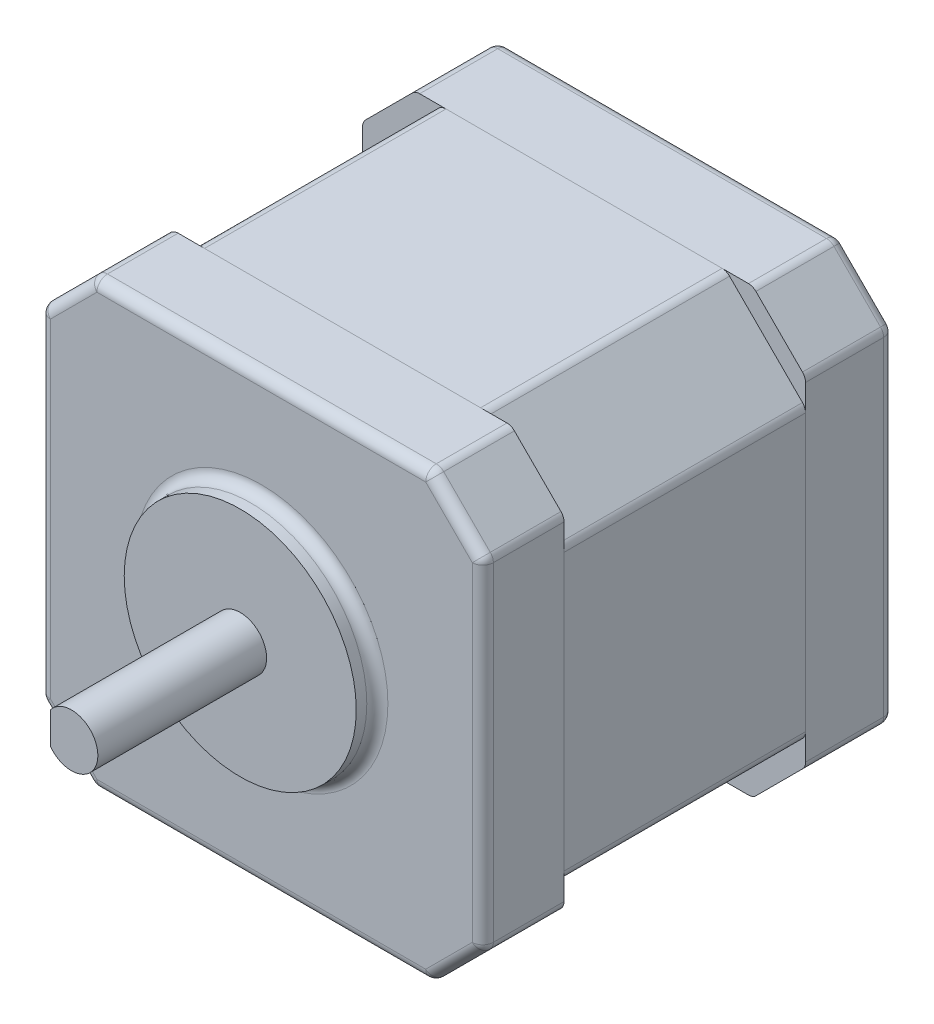
SolidWorks part; units mm, degrees
material "AISI 1020"
ref_plane "Front Plane" through (0, 0, 0) normal (0, 0, 1) x (1, 0, 0)
ref_plane "Top Plane" through (0, 0, 0) normal (0, 1, 0) x (1, 0, 0)
ref_plane "Right Plane" through (0, 0, 0) normal (1, 0, 0) x (0, 0, -1)
sketch "Sketch1" plane through (0, 0, 0) normal (0, 0, 1) x (1, 0, 0)
  line L1 (-21, -21) -> (21, -21)
  line L2 (-21, -21) -> (-21, 21)
  line L3 (-21, 21) -> (21, 21)
  line L4 (21, -21) -> (21, 21)
  line L5 (-21, -21) -> (21, 21) construction
  line L6 (-21, 21) -> (21, -21) construction
  point P0 (0, 0)
  dimension "D1" = 42
extrude "Boss-Extrude1" add sketch "Sketch1" along normal mid plane 39
sketch "Sketch2" plane through (0, 0, 19.5) normal (0, 0, 1) x (1, 0, 0)
  line L0 (-21, 21) -> (-13.5, 21)
  line L1 (21, 21) -> (-21, 21) construction
  line L2 (-13.5, 21) -> (-21, 13.5)
  line L3 (-21, 21) -> (-21, -21) construction
  line L4 (-21, 13.5) -> (-21, 21)
  line L5 (13.5, 21) -> (21, 21)
  line L6 (21, 13.5) -> (13.5, 21)
  line L7 (21, 21) -> (21, 13.5)
  line L8 (21, -13.5) -> (21, -21)
  line L9 (13.5, -21) -> (21, -13.5)
  line L10 (21, -21) -> (13.5, -21)
  line L11 (-13.5, -21) -> (-21, -21)
  line L12 (-21, -13.5) -> (-13.5, -21)
  line L13 (-21, -21) -> (-21, -13.5)
  line L14 (0, 0) -> (-13.5, 21) construction
  line L15 (-21, -21) -> (21, -21) construction
  dimension "D1" = 7.5
  dimension "D3" = 24.965
  dimension "D2" = 4
extrude "Cut-Extrude1" cut sketch "Sketch2" against normal blind 22.9 from offset 7.7 offset against normal yes
sketch "Sketch3" plane through (0, 0, 19.5) normal (0, 0, 1) x (1, 0, 0)
  circle A0 centre (0, 0) radius 11
  dimension "D1" = 22
extrude "Boss-Extrude2" add sketch "Sketch3" along normal blind 2
chamfer "Chamfer1" distance 5 angle 45 8 edges at (21, 21, -15.3) (21, 21, 15.65) (21, -21, 15.65) (21, -21, -15.3) (-21, 21, -15.3) (-21, -21, -15.3) (-21, -21, 15.65) (-21, 21, 15.65)
fillet "Fillet1" radius 1 41 edges at (-18.5, 18.5, -19.5) (-21, 0, -19.5) (-18.5, -18.5, -19.5) (0, -21, -19.5) (18.5, -18.5, -19.5) (21, 0, -19.5) (18.5, 18.5, -19.5) (0, 21, -19.5) (18.5, -18.5, 19.5) (0, -21, 19.5) (-18.5, -18.5, 19.5) (-21, 0, 19.5) (-18.5, 18.5, 19.5) (0, 21, 19.5) (18.5, 18.5, 19.5) (21, 0, 19.5) (11, 0, 19.5) (-21, 16, 15.65) (-16, 21, 15.65) (-16, 21, -15.3) (-21, 16, -15.3) (-21, 13.5, 0.35) (-13.5, 21, 0.35) (16, 21, 15.65) (21, 16, 15.65) (21, 16, -15.3) (16, 21, -15.3) (13.5, 21, 0.35) (21, 13.5, 0.35) (21, -16, 15.65) (16, -21, 15.65) (21, -13.5, 0.35) (13.5, -21, 0.35) (16, -21, -15.3) (21, -16, -15.3) (-16, -21, -15.3) (-21, -16, -15.3) (-13.5, -21, 0.35) (-21, -13.5, 0.35) (-21, -16, 15.65) (-16, -21, 15.65)
sketch "Sketch4" plane through (0, 0, 21.5) normal (0, 0, 1) x (1, 0, 0)
  line L0 (-2, -1.5) -> (-2, 1.5)
  arc A0 (-2, -1.5) -> (-2, 1.5) centre (0, 0) ccw
  dimension "D1" = 5
  dimension "D2" = 2
extrude "Boss-Extrude3" add sketch "Sketch4" along normal blind 16
sketch "Sketch6" plane through (-21, 0, 0) normal (-1, 0, 0) x (0, 0, 1)
  line L0 (-11.1, -20.7071) -> (-11.1, -13.7929) construction
  line L1 (-11.1, 13.7929) -> (-11.1, 20.7071) construction
  line L2 (11.8, -20.7071) -> (11.8, -13.7929) construction
  line L3 (11.8, 13.7929) -> (11.8, 20.7071) construction
  line L4 (-11.1, -20.7071) -> (-11.1, -13.7929)
  line L5 (-11.1, 13.7929) -> (-11.1, 20.7071)
  line L6 (11.8, -20.7071) -> (11.8, -13.7929)
  line L7 (11.8, 13.7929) -> (11.8, 20.7071)
  line L8 (11.8, 13.7929) -> (11.8, -13.7929)
  line L9 (-11.1, 13.7929) -> (-11.1, -13.7929)
split line "Split Line1"
sketch "Sketch7" plane through (0, -21, 0) normal (0, -1, 0) x (1, 0, 0)
  line L0 (-13.7929, -11.1) -> (-20.7071, -11.1) construction
  line L1 (20.7071, -11.1) -> (13.7929, -11.1) construction
  line L2 (20.7071, 11.8) -> (13.7929, 11.8) construction
  line L3 (-13.7929, 11.8) -> (-20.7071, 11.8) construction
  line L4 (-13.7929, -11.1) -> (-20.7071, -11.1)
  line L5 (20.7071, -11.1) -> (13.7929, -11.1)
  line L6 (20.7071, 11.8) -> (13.7929, 11.8)
  line L7 (-13.7929, 11.8) -> (-20.7071, 11.8)
  line L8 (-13.7929, 11.8) -> (13.7929, 11.8)
  line L9 (13.7929, -11.1) -> (-13.7929, -11.1)
split line "Split Line2"
